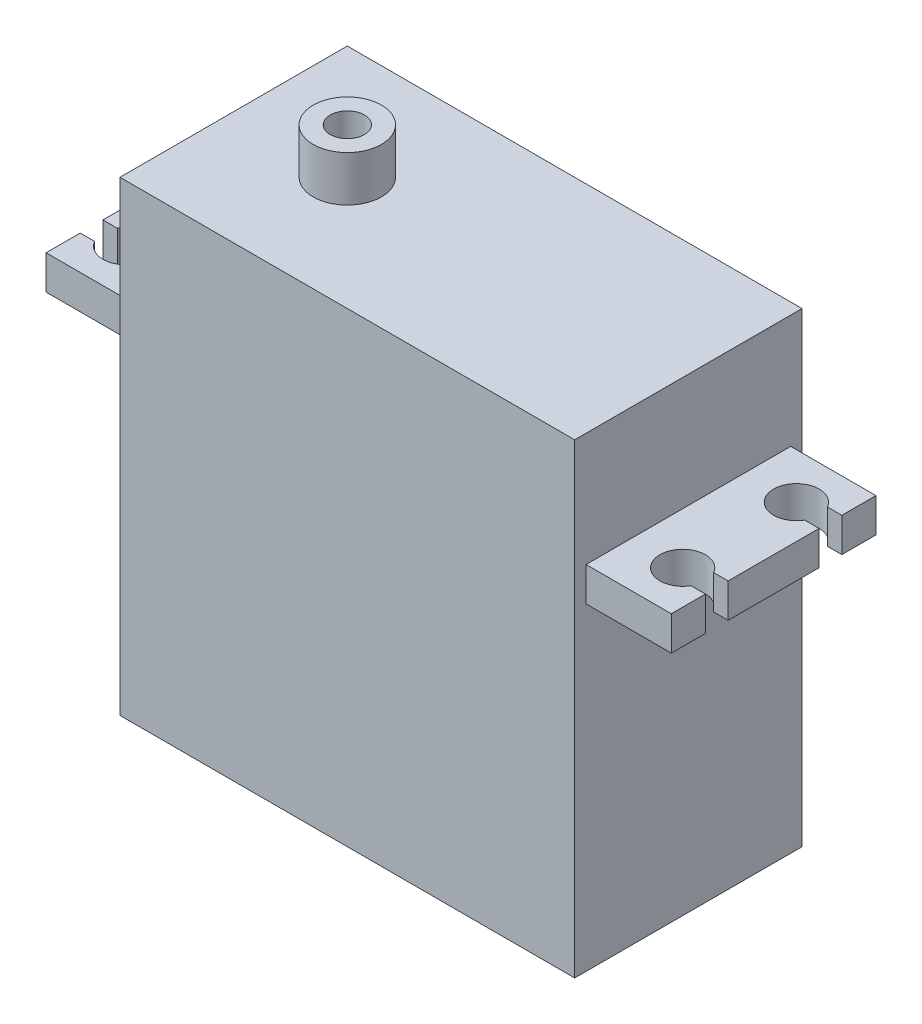
SolidWorks part; units mm, degrees
ref_plane "Front Plane" through (0, 0, 0) normal (0, 0, 1) x (1, 0, 0)
ref_plane "Top Plane" through (0, 0, 0) normal (0, 1, 0) x (1, 0, 0)
ref_plane "Right Plane" through (0, 0, 0) normal (1, 0, 0) x (0, 0, -1)
sketch "Sketch1" plane through (0, 0, 0) normal (0, 1, 0) x (1, 0, 0)
  line L1 (-20, 10) -> (20, 10)
  line L2 (-20, 10) -> (-20, -10)
  line L3 (-20, -10) -> (20, -10)
  line L4 (20, 10) -> (20, -10)
  line L5 (-20, 10) -> (20, -10) construction
  line L6 (-20, -10) -> (20, 10) construction
  point P0 (0, 0)
  dimension "D1" = 40
  dimension "D2" = 20
extrude "Body" add sketch "Sketch1" along normal blind 41
ref_plane "Plane1" through (0, 28, 0) normal (0, 1, 0) x (1, 0, 0)
sketch "Sketch2" plane through (0, 28, 0) normal (0, 1, 0) x (1, 0, 0)
  line L1 (-27.5, 9) -> (27.5, 9)
  line L2 (-27.5, 9) -> (-27.5, -9)
  line L3 (-27.5, -9) -> (27.5, -9)
  line L4 (27.5, 9) -> (27.5, -9)
  line L5 (-27.5, 9) -> (27.5, -9) construction
  line L6 (-27.5, -9) -> (27.5, 9) construction
  point P0 (0, 0)
  dimension "D1" = 18
  dimension "D2" = 55
extrude "Fin" add sketch "Sketch2" along normal blind 3
sketch "Sketch3" plane through (0, 28, 0) normal (0, 1, 0) x (1, 0, 0)
  line L1 (0, -11) -> (0, 11) construction
  line L2 (-27.5, -9) -> (-20, -9) construction
  line L3 (-20, 9) -> (-27.5, 9) construction
  line L4 (-27.5, 9) -> (-27.5, -9) construction
  circle A0 centre (-24.5, 5) radius 2
  circle A1 centre (-24.5, -5) radius 2
  circle A2 centre (24.5, -5) radius 2
  circle A3 centre (24.5, 5) radius 2
  dimension "D1" = 4
  dimension "D2" = 4
  dimension "D3" = 10
  dimension "D4" = 3
  dimension "D5" = 4
  dimension "D6" = 4
extrude "Hole for screws" cut sketch "Sketch3" along normal up to next
ref_plane "Plane2" through (-20, 0, 0) normal (-1, 0, 0) x (0, 0, 1)
sketch "Sketch4" plane through (-20, 0, 0) normal (-1, 0, 0) x (0, 0, 1)
  line L0 (-10, 0) -> (10, 0) construction
  line L1 (-3.5, 7) -> (3.5, 7)
  line L2 (-3.5, 7) -> (-3.5, 3)
  line L3 (-3.5, 3) -> (3.5, 3)
  line L4 (3.5, 7) -> (3.5, 3)
  line L5 (-3.5, 7) -> (3.5, 3) construction
  line L6 (-3.5, 3) -> (3.5, 7) construction
  point P0 (0, 5)
  dimension "D1" = 7
  dimension "D2" = 3
  dimension "D3" = 4
extrude "Wire out" add sketch "Sketch4" along normal blind 0.5
ref_plane "Plane3" through (0, 41, 0) normal (0, 1, 0) x (1, 0, 0)
sketch "Sketch5" plane through (0, 41, 0) normal (0, 1, 0) x (1, 0, 0)
  line L0 (-20, 11) -> (-20, -11) construction
  line L1 (-20, -10) -> (20, -10) construction
  circle A0 centre (-10, 0) radius 10 construction
  circle A1 centre (-10, 0) radius 3
  dimension "D1" = 6
  dimension "D2" = 10
  dimension "D3" = 10
extrude "Axle" add sketch "Sketch5" along normal blind 4
ref_plane "Plane4" through (0, 45, 0) normal (0, 1, 0) x (1, 0, 0)
sketch "Sketch6" plane through (0, 45, 0) normal (0, 1, 0) x (1, 0, 0)
  circle A0 centre (-10, 0) radius 1.5
  dimension "D1" = 3
extrude "Cut-Extrude1" cut sketch "Sketch6" against normal blind 4 contours A0
sketch "Sketch8" plane through (0, 28, 0) normal (0, 1, 0) x (1, 0, 0)
  line L0 (-26, 6) -> (-28, 6)
  line L1 (-28, 6) -> (-28, 4)
  line L2 (-28, 4) -> (-26, 4)
  line L3 (-26, 4) -> (-26, 6)
  line L4 (-20, 9) -> (-27.5, 9) construction
  line L8 (-24.75, 0) -> (24.75, 0) construction
  line L9 (-26, -6) -> (-28, -6)
  line L10 (-26, -4) -> (-26, -6)
  line L11 (-28, -4) -> (-26, -4)
  line L12 (-28, -6) -> (-28, -4)
  line L13 (0, -11) -> (0, 11) construction
  line L14 (28, -6) -> (28, -4)
  line L15 (28, -4) -> (26, -4)
  line L16 (26, -4) -> (26, -6)
  line L17 (26, -6) -> (28, -6)
  line L18 (26, 6) -> (28, 6)
  line L19 (28, 6) -> (28, 4)
  line L20 (28, 4) -> (26, 4)
  line L21 (26, 4) -> (26, 6)
  line L22 (-20, 10) -> (-20, -10) construction
  dimension "D1" = 2
  dimension "D2" = 2
  dimension "D3" = 3
  dimension "D4" = 6
extrude "Cut-Extrude4" cut sketch "Sketch8" along normal up to next
sketch "Sketch9" plane through (0, 45, 0) normal (0, 1, 0) x (1, 0, 0)
  point P0 (-10, 0)
sketch "Sketch10" plane through (0, 0, 0) normal (0, 1, 0) x (1, 0, 0)
  point P0 (-10, 0)
sketch3d "3DSketch1"
  line L0 (-10, 45, 0) -> (-10, -49955, 0) construction
